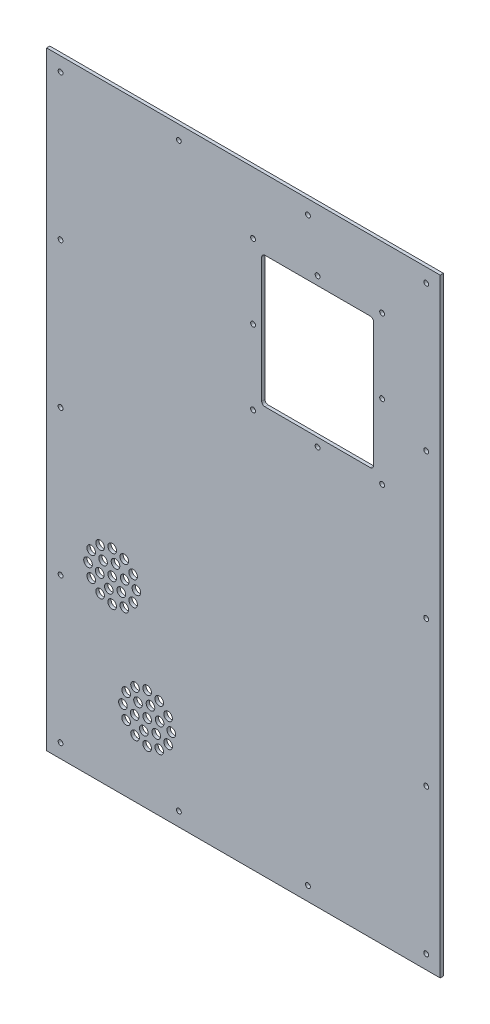
SolidWorks part; units mm, degrees
ref_plane "Спереди" through (0, 0, 0) normal (0, 0, 1) x (1, 0, 0)
ref_plane "Сверху" through (0, 0, 0) normal (0, 1, 0) x (1, 0, 0)
ref_plane "Справа" through (0, 0, 0) normal (1, 0, 0) x (0, 0, -1)
sketch "Эскиз1" plane through (0, 0, 0) normal (0, 0, 1) x (1, 0, 0)
  line L0 (0, 0) -> (366, 0)
  line L1 (0, 0) -> (0, 566)
  line L2 (366, 0) -> (366, 566)
  line L3 (0, 566) -> (366, 566)
  dimension "D1" = 566
  dimension "D2" = 366
extrude "Бобышка-Вытянуть1" add sketch "Эскиз1" along normal blind 3
sketch "Эскиз2" plane through (0, 0, 3) normal (0, 0, 1) x (1, 0, 0)
  line L0 (3, 563) -> (363, 563) construction
  line L1 (3, 563) -> (3, 3) construction
  line L2 (363, 563) -> (363, 3) construction
  line L3 (3, 3) -> (363, 3) construction
  line L4 (0, 566) -> (0, 0) construction
  line L5 (0, 0) -> (366, 0) construction
  dimension "D1" = 560
  dimension "D2" = 360
  dimension "D3" = 3
  dimension "D4" = 3
sketch "Эскиз5" plane through (0, 0, 0) normal (0, 0, -1) x (-1, 0, 0)
  line L0 (-353, 553) -> (-13, 553) construction
  line L1 (-353, 553) -> (-353, 13) construction
  line L2 (-13, 553) -> (-13, 13) construction
  line L3 (-353, 13) -> (-13, 13) construction
  line L4 (-366, 566) -> (0, 566) construction
  line L5 (-366, 0) -> (-366, 566) construction
  line L6 (0, 566) -> (0, 0) construction
  line L7 (0, 0) -> (-366, 0) construction
  line L8 (-366, 23) -> (-343, 23) construction
  line L9 (-366, 23) -> (-366, 0) construction
  line L10 (-343, 23) -> (-343, 0) construction
  line L11 (-366, 0) -> (-343, 0) construction
  line L12 (0, 0) -> (0, 23) construction
  line L13 (0, 0) -> (-23, 0) construction
  line L14 (0, 23) -> (-23, 23) construction
  line L15 (-23, 0) -> (-23, 23) construction
  line L16 (-366, 566) -> (-343, 566) construction
  line L17 (-366, 566) -> (-366, 543) construction
  line L18 (-343, 566) -> (-343, 543) construction
  line L19 (-366, 543) -> (-343, 543) construction
  line L20 (0, 566) -> (0, 543) construction
  line L21 (0, 566) -> (-23, 566) construction
  line L22 (0, 543) -> (-23, 543) construction
  line L23 (-23, 566) -> (-23, 543) construction
  line L24 (-13, 283) -> (-353, 283) construction
  line L25 (-183, 553) -> (-183, 13) construction
  circle A0 centre (-353, 553) radius 2.25
  circle A1 centre (-13, 553) radius 2.25
  circle A3 centre (-243, 553) radius 2.25
  circle A4 centre (-123, 553) radius 2.25
  circle A5 centre (-353, 418) radius 2.25
  circle A6 centre (-353, 283) radius 2.25
  circle A7 centre (-353, 148) radius 2.25
  circle A8 centre (-353, 13) radius 2.25
  circle A11 centre (-13, 418) radius 2.25
  circle A12 centre (-13, 283) radius 2.25
  circle A13 centre (-13, 148) radius 2.25
  circle A14 centre (-13, 13) radius 2.25
  circle A18 centre (-123, 13) radius 2.25
  circle A19 centre (-243, 13) radius 2.25
  dimension "D13" = 4.5
  dimension "D14" = 4.5
  dimension "D15" = 110
  dimension "D17" = 4.5
  dimension "D18" = 4.5
  dimension "D19" = 110
  dimension "D22" = 135
  dimension "D23" = 135
  dimension "D24" = 110
  dimension "D25" = 5
  dimension "D26" = 135
  dimension "D27" = 110
  dimension "D29" = 4.5
  dimension "D31" = 4.5
  dimension "D1" = 13
  dimension "D2" = 13
  dimension "D3" = 13
  dimension "D4" = 13
  dimension "D5" = 23
  dimension "D6" = 23
  dimension "D7" = 23
  dimension "D8" = 23
  dimension "D9" = 23
  dimension "D10" = 23
  dimension "D11" = 23
  dimension "D12" = 23
  dimension "D21" = 5
extrude "Вырез-Вытянуть2" cut sketch "Эскиз5" against normal through all
sketch "Эскиз6" plane through (0, 0, 3) normal (0, 0, 1) x (1, 0, 0)
  line L0 (200, 378.5) -> (200, 500.5) construction
  line L1 (200, 378.5) -> (200, 500.5)
  line L2 (200, 500.5) -> (304, 500.5) construction
  line L3 (200, 500.5) -> (304, 500.5)
  line L4 (304, 500.5) -> (304, 378.5) construction
  line L5 (304, 500.5) -> (304, 378.5)
  line L6 (304, 378.5) -> (200, 378.5) construction
  line L7 (304, 378.5) -> (200, 378.5)
extrude "Вырез-Вытянуть3" cut sketch "Эскиз6" against normal through all
sketch "Эскиз7" plane through (0, 0, 3) normal (0, 0, 1) x (1, 0, 0)
  circle A0 centre (192, 370.5) radius 2.25 construction
  circle A1 centre (192, 370.5) radius 2.25
  circle A2 centre (192, 439.5) radius 2.25 construction
  circle A3 centre (192, 439.5) radius 2.25
  circle A4 centre (192, 508.5) radius 2.25 construction
  circle A5 centre (192, 508.5) radius 2.25
  circle A6 centre (252, 370.5) radius 2.25 construction
  circle A7 centre (252, 370.5) radius 2.25
  circle A8 centre (312, 370.5) radius 2.25 construction
  circle A9 centre (312, 370.5) radius 2.25
  circle A10 centre (252, 508.5) radius 2.25 construction
  circle A11 centre (252, 508.5) radius 2.25
  circle A12 centre (312, 508.5) radius 2.25 construction
  circle A13 centre (312, 508.5) radius 2.25
  circle A14 centre (312, 439.5) radius 2.25 construction
  circle A15 centre (312, 439.5) radius 2.25
  circle A16 centre (312, 370.5) radius 2.25
extrude "Вырез-Вытянуть4" cut sketch "Эскиз7" against normal through all contours A3 | A11 | A13 | A15 | A9 | A7 | A1 | A5 region at (192, 370.5, 3) region at (192, 439.5, 3) region at (252, 370.5, 3) region at (312, 370.5, 3) region at (252, 508.5, 3) region at (312, 508.5, 3) region at (312, 439.5, 3)
fillet "Fillet2" radius 3 4 edges at (200, 378.5, 1.5) (304, 378.5, 1.5) (304, 500.5, 1.5) (200, 500.5, 1.5)
sketch "Эскиз8" plane through (0, 0, 0) normal (0, 0, -1) x (-1, 0, 0)
  line L0 (-93.5, 73) -> (-93.5, 0) construction
  line L1 (0, 0) -> (-366, 0) construction
  line L2 (-61, 171) -> (0, 171) construction
  line L3 (0, 566) -> (0, 0) construction
  line L4 (-93.5, 73) -> (0, 73) construction
  line L5 (-61, 171) -> (-76.9099, 155.0901) construction
  line L6 (-93.5, 73) -> (-101.9853, 64.5147) construction
  line L7 (-61, 193.5) -> (-61, 148.5) construction
  circle A0 centre (-61, 171) radius 12 construction
  circle A1 centre (-61, 171) radius 22.5 construction
  circle A2 centre (-61, 148.5) radius 4
  circle A3 centre (-69.4853, 162.5147) radius 4
  circle A4 centre (-61, 171) radius 4
  circle A5 centre (-72.25, 151.5144) radius 4
  circle A6 centre (-80.4856, 159.75) radius 4
  circle A7 centre (-83.5, 171) radius 4
  circle A8 centre (-80.4856, 182.25) radius 4
  circle A9 centre (-72.25, 190.4856) radius 4
  circle A10 centre (-61, 193.5) radius 4
  circle A11 centre (-49.75, 190.4856) radius 4
  circle A12 centre (-41.5144, 182.25) radius 4
  circle A13 centre (-38.5, 171) radius 4
  circle A14 centre (-41.5144, 159.75) radius 4
  circle A15 centre (-49.75, 151.5144) radius 4
  circle A16 centre (-72.5911, 174.1058) radius 4
  circle A17 centre (-64.1058, 182.5911) radius 4
  circle A18 centre (-52.5147, 179.4853) radius 4
  circle A19 centre (-49.4089, 167.8942) radius 4
  circle A20 centre (-57.8942, 159.4089) radius 4
  circle A21 centre (-93.5, 73) radius 12 construction
  circle A22 centre (-93.5, 73) radius 22.5 construction
  circle A23 centre (-93.5, 73) radius 4
  circle A24 centre (-93.5, 50.5) radius 4
  circle A25 centre (-101.9853, 64.5147) radius 4
  circle A26 centre (-104.75, 53.5144) radius 4
  circle A27 centre (-112.9856, 61.75) radius 4
  circle A28 centre (-116, 73) radius 4
  circle A29 centre (-112.9856, 84.25) radius 4
  circle A30 centre (-104.75, 92.4856) radius 4
  circle A31 centre (-93.5, 95.5) radius 4
  circle A32 centre (-82.25, 92.4856) radius 4
  circle A33 centre (-74.0144, 84.25) radius 4
  circle A34 centre (-71, 73) radius 4
  circle A35 centre (-74.0144, 61.75) radius 4
  circle A36 centre (-82.25, 53.5144) radius 4
  circle A37 centre (-105.0911, 76.1058) radius 4
  circle A38 centre (-96.6058, 84.5911) radius 4
  circle A39 centre (-85.0147, 81.4853) radius 4
  circle A40 centre (-81.9089, 69.8942) radius 4
  circle A41 centre (-90.3942, 61.4089) radius 4
  point P26 (-61, 171)
  point P52 (-61, 171)
  point P82 (-93.5, 73)
  point P93 (-93.5, 73)
  dimension "D4" = 45
  dimension "D5" = 24
  dimension "D7" = 8
  dimension "D8" = 8
  dimension "D9" = 8
  dimension "D12" = 8
  dimension "D13" = 8
  dimension "D14" = 8
  dimension "D16" = 24
  dimension "D17" = 45
  dimension "D1" = 73
  dimension "D2" = 61
  dimension "D3" = 93.5
  dimension "D6" = 45
  dimension "D15" = 171
  dimension "D20" = 45
  dimension "D10" = 12
  dimension "D11" = 6
  dimension "D18" = 12
  dimension "D19" = 6
extrude "Вырез-Вытянуть5" cut sketch "Эскиз8" against normal through all
